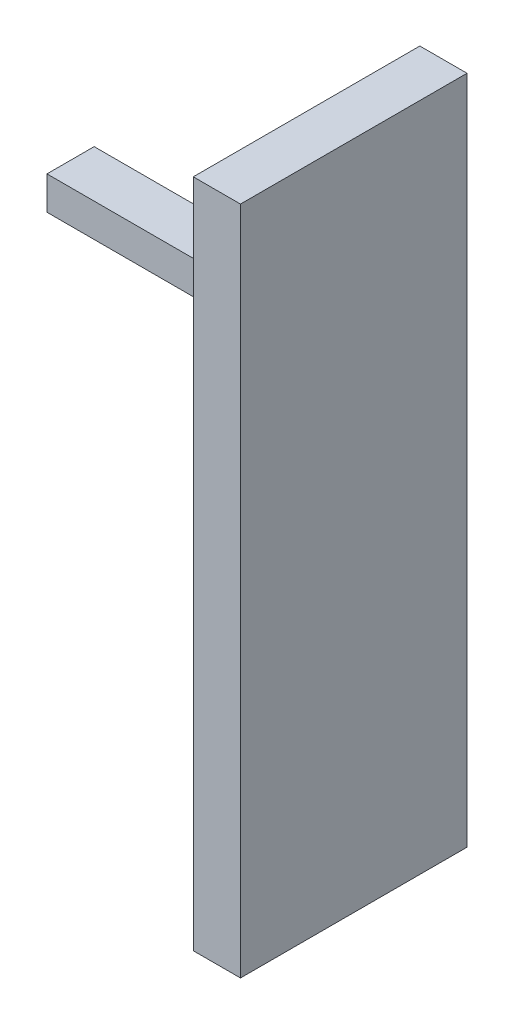
SolidWorks part; units mm, degrees
ref_plane "Front Plane" through (0, 0, 0) normal (1, 0, 0) x (0, 1, 0)
ref_plane "Top Plane" through (0, 0, 0) normal (0, 0, 1) x (0, 1, 0)
ref_plane "Right Plane" through (0, 0, 0) normal (0, 1, 0) x (-1, 0, 0)
sketch "Sketch2" plane through (0, 0, 0) normal (1, 0, 0) x (0, 1, 0)
  line L0 (45.5, 24) -> (18.7, 24) construction
  line L1 (-31.5, 24) -> (110.5095, 24)
  line L2 (-31.5, 24) -> (-31.5, -24)
  line L3 (-31.5, -24) -> (110.5095, -24)
  line L4 (110.5095, 24) -> (110.5095, -24)
  line L5 (-31.5, 24) -> (110.5095, -24) construction
  line L6 (-31.5, -24) -> (110.5095, 24) construction
  line L11 (-31.5, 6) -> (-31.5, -6) construction
  point P0 (6.1229, -11.2832)
  dimension "D1" = 0
  dimension "D2" = 0
extrude "Boss-Extrude1" add sketch "Sketch2" along normal blind 10
sketch "Sketch3" plane through (0, 0, 0) normal (-1, 0, 0) x (0, -1, 0)
  circle A0 centre (-14, 13) radius 2.65
  circle A1 centre (13.9762, 13) radius 2.65
  circle A2 centre (13.9762, -13) radius 2.65
  circle A3 centre (-14, -13) radius 2.65
  point P0 (13.9762, 13)
  point P1 (13.9762, -13)
  point P2 (-14, -13)
  point P3 (-14, 13)
  dimension "D1" = 5.3
  dimension "D2" = 5.3
  dimension "D3" = 5.3
  dimension "D4" = 5.3
extrude "Cut-Extrude1" cut sketch "Sketch3" against normal blind 7
sketch "Sketch4" plane through (0, 0, 0) normal (-1, 0, 0) x (0, -1, 0)
  line L0 (-65.5, 5) -> (-65.5, -5) construction
  line L1 (-69.5, 5) -> (-76.5473, 5)
  line L2 (-69.5, 5) -> (-69.5, -5)
  line L3 (-69.5, -5) -> (-76.5473, -5)
  line L4 (-76.5473, 5) -> (-76.5473, -5)
  line L5 (-69.5, 5) -> (-76.5473, -5) construction
  line L6 (-69.5, -5) -> (-76.5473, 5) construction
  point P0 (-73.0236, 0)
  dimension "D1" = 4
  dimension "D2" = 10
  dimension "D3" = 0
extrude "Boss-Extrude2" add sketch "Sketch4" along normal blind 50
